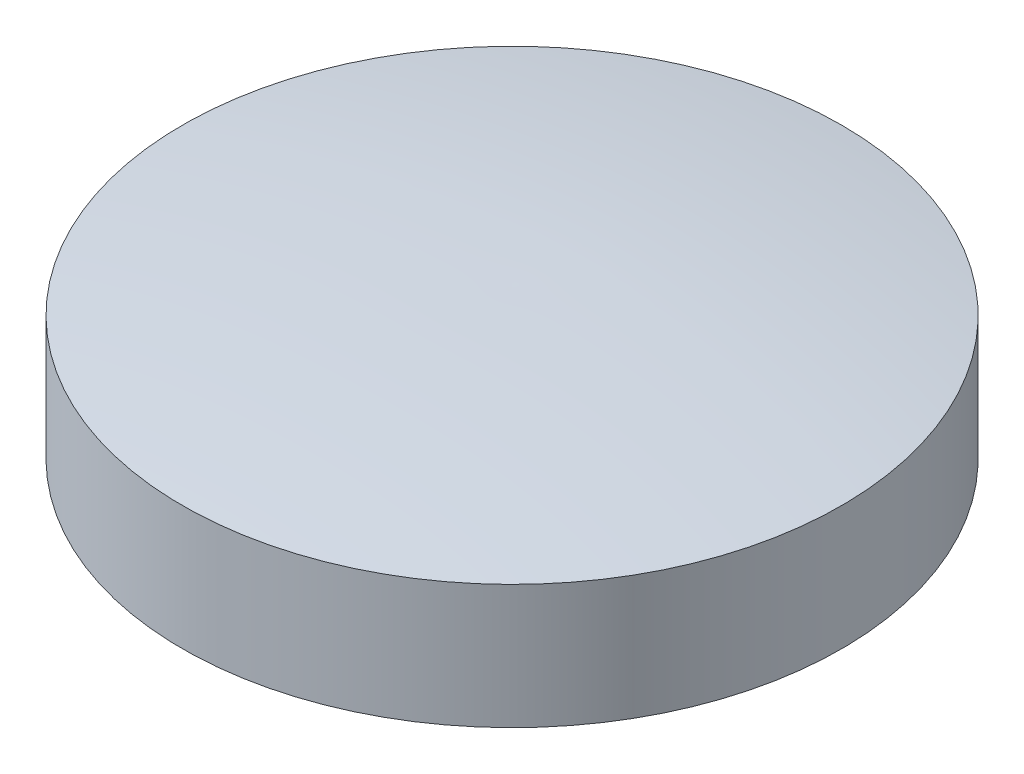
SolidWorks part; units mm, degrees
material "Glas"
ref_plane "Front" through (0, 0, 0) normal (0, 0, 1) x (1, 0, 0)
ref_plane "Top" through (0, 0, 0) normal (0, 1, 0) x (1, 0, 0)
ref_plane "Right" through (0, 0, 0) normal (1, 0, 0) x (0, 0, -1)
sketch "Skizze3" plane through (0, 0, 0) normal (1, 0, 0) x (0, 0, -1)
  line L0 (0, 0) -> (0, 14.7875) construction
  line L1 (0, 0) -> (25.5, 0)
  line L2 (25.5, 0) -> (25.5, 9.6)
  line L4 (0, 11.5159) -> (0, 0)
  arc A0 (25.5, 9.6) -> (0, 11.5159) centre (1.0338, -145.3851) ccw
  point P7 (0, 11.5159)
  dimension "D1" = 51
  dimension "D2" = 9.6
revolve "Rotation1" add sketch "Skizze3" angle 360 about L0
